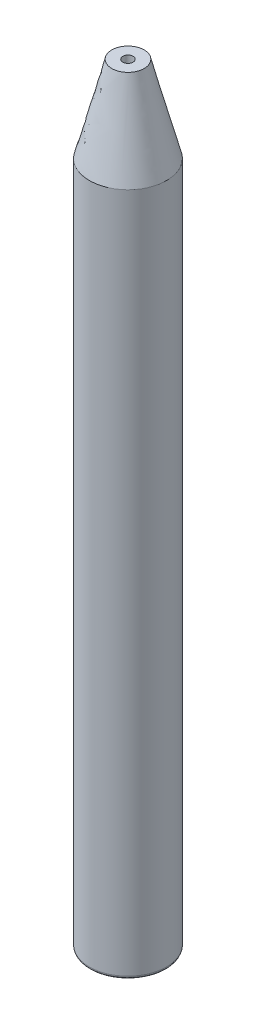
SolidWorks part; units mm, degrees
material "Plain Carbon Steel"
ref_plane "Front Plane" through (0, 0, 0) normal (0, 0, 1) x (1, 0, 0)
ref_plane "Top Plane" through (0, 0, 0) normal (0, 1, 0) x (1, 0, 0)
ref_plane "Right Plane" through (0, 0, 0) normal (1, 0, 0) x (0, 0, -1)
sketch "Sketch1" plane through (0, 0, 0) normal (0, 1, 0) x (1, 0, 0)
  circle A0 centre (0, 0) radius 3.81
  dimension "D1" = 7.62
extrude "Boss-Extrude1" add sketch "Sketch1" along normal blind 67.7
sketch "Sketch2" plane through (0, 67.7, 0) normal (0, 1, 0) x (1, 0, 0)
  circle A0 centre (0, 0) radius 3.81 construction
  circle A1 centre (0, 0) radius 3.81
ref_plane "Plane1" through (0, 76.2, 0) normal (0, 1, 0) x (1, 0, 0)
sketch "Sketch3" plane through (0, 76.2, 0) normal (0, 1, 0) x (1, 0, 0)
  circle A0 centre (0, 0) radius 1.6
  dimension "D1" = 3.2
loft "Loft1" add profiles "Sketch3", "Sketch2" connector at (1.216, 76.2, 1.0399) connector at (2.3181, 67.7, 3.0236)
sketch "Sketch5" plane through (0, 76.2, 0) normal (0, 1, 0) x (1, 0, 0)
  circle A0 centre (0, 0) radius 0.508
  dimension "D1" = 1.016
extrude "Cut-Extrude2" cut sketch "Sketch5" against normal through all
sketch "Sketch7" plane through (0, 0, 0) normal (0, -1, 0) x (1, 0, 0)
  circle A2 centre (0, 0) radius 2.61
  circle A3 centre (0, 0) radius 2.61
  dimension "D1" = 1.2
extrude "Cut-Extrude3" cut sketch "Sketch7" against normal blind 6 draft 19.33 contours A3
fillet "Fillet3" radius 0.3 1 edges at (0, 0, 3.81) tangent propagation no
